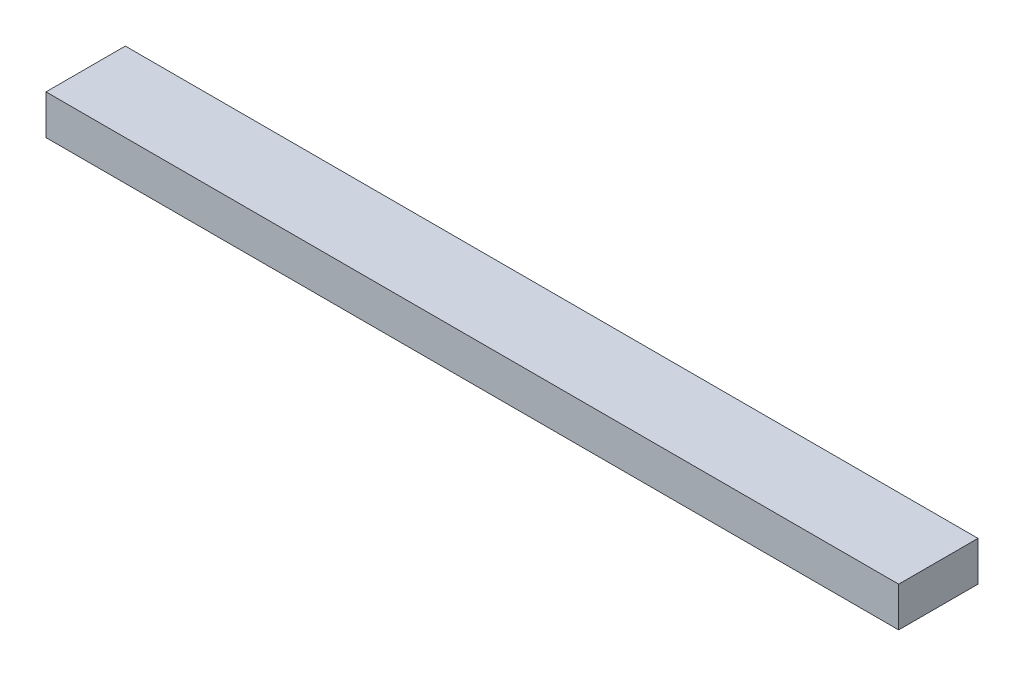
SolidWorks part; units mm, degrees
material "1023 Carbon Steel Sheet (SS)"
ref_plane "Front Plane" through (0, 0, 0) normal (0, 0, 1) x (1, 0, 0)
ref_plane "Top Plane" through (0, 0, 0) normal (0, 1, 0) x (1, 0, 0)
ref_plane "Right Plane" through (0, 0, 0) normal (1, 0, 0) x (0, 0, -1)
sketch "Sketch1" plane through (0, 0, 0) normal (1, 0, 0) x (0, 0, -1)
  line L1 (0, 0) -> (101.6, 0)
  line L2 (0, 0) -> (0, 50.8)
  line L3 (0, 50.8) -> (101.6, 50.8)
  line L4 (101.6, 0) -> (101.6, 50.8)
  dimension "D1" = 50.8
  dimension "D2" = 101.6
extrude "Boss-Extrude1" add sketch "Sketch1" along normal blind 1092.2
